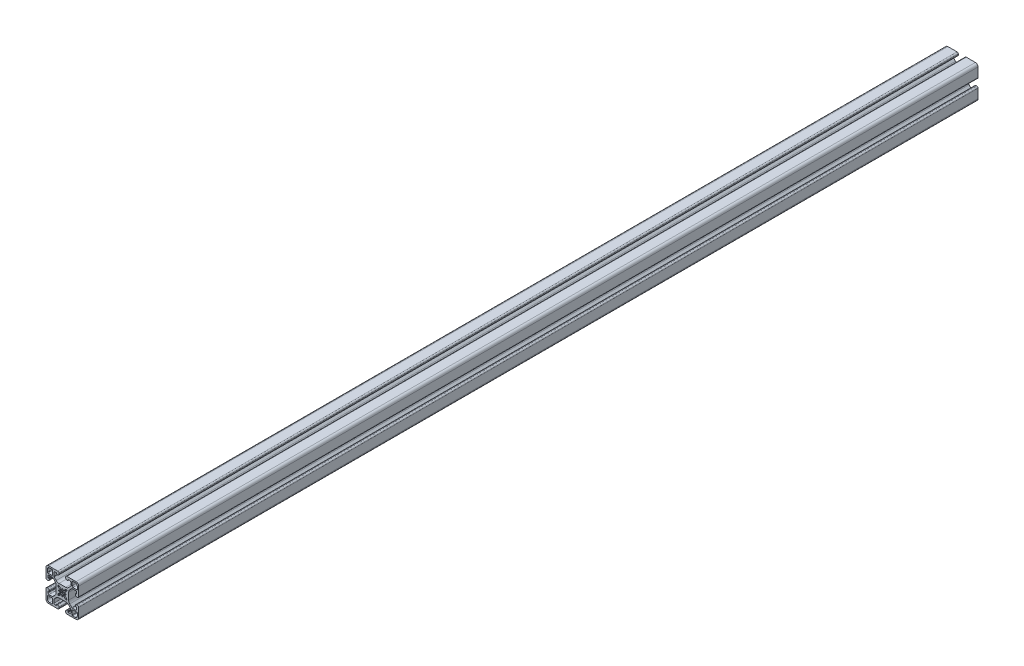
SolidWorks part; units mm, degrees
material "6005A-T61 Aluminum"
ref_plane "Front Plane" through (0, 0, 0) normal (0, 0, 1) x (1, 0, 0)
ref_plane "Top Plane" through (0, 0, 0) normal (0, 1, 0) x (1, 0, 0)
ref_plane "Right Plane" through (0, 0, 0) normal (1, 0, 0) x (0, 0, -1)
sketch "Sketch1" plane through (0, 0, 0) normal (0, 0, 1) x (1, 0, 0)
  line L0 (-5.1263, -3.712) -> (-5.4393, -4.8481)
  line L1 (-3.0049, -1.5907) -> (-5.1263, -3.712)
  line L2 (-4.0876, -0.4923) -> (-3.3421, -0.625)
  line L3 (-3.3421, 0.625) -> (-4.0876, 0.4923)
  line L4 (-5.1263, 3.712) -> (-3.0049, 1.5907)
  line L5 (-5.4393, 4.8481) -> (-5.1263, 3.712)
  line L6 (-3.712, 5.1263) -> (-4.8481, 5.4393)
  line L7 (-1.5907, 3.0049) -> (-3.712, 5.1263)
  line L8 (-0.4923, 4.0876) -> (-0.625, 3.3421)
  line L9 (0.625, 3.3421) -> (0.4923, 4.0876)
  line L10 (3.712, 5.1263) -> (1.5907, 3.0049)
  line L11 (4.8481, 5.4393) -> (3.712, 5.1263)
  line L12 (5.1263, 3.712) -> (5.4393, 4.8481)
  line L13 (3.0049, 1.5907) -> (5.1263, 3.712)
  line L14 (4.0876, 0.4923) -> (3.3421, 0.625)
  line L15 (3.3421, -0.625) -> (4.0876, -0.4923)
  line L16 (5.1263, -3.712) -> (3.0049, -1.5907)
  line L17 (5.4393, -4.8481) -> (5.1263, -3.712)
  line L18 (3.712, -5.1263) -> (4.8481, -5.4393)
  line L19 (1.5907, -3.0049) -> (3.712, -5.1263)
  line L20 (0.4923, -4.0876) -> (0.625, -3.3421)
  line L21 (-0.625, -3.3421) -> (-0.4923, -4.0876)
  line L22 (-3.712, -5.1263) -> (-1.5907, -3.0049)
  line L23 (-4.8481, -5.4393) -> (-3.712, -5.1263)
  line L24 (-12.4898, 18.345) -> (-15.545, 18.345)
  line L25 (-11.8598, 13.1298) -> (-11.8598, 17.715)
  line L26 (-17.715, 11.8598) -> (-13.1298, 11.8598)
  line L27 (-18.345, 15.545) -> (-18.345, 12.4898)
  line L28 (18.345, 12.4898) -> (18.345, 15.545)
  line L29 (13.1298, 11.8598) -> (17.715, 11.8598)
  line L30 (11.8598, 17.715) -> (11.8598, 13.1298)
  line L31 (15.545, 18.345) -> (12.4898, 18.345)
  line L32 (-18.345, -12.4898) -> (-18.345, -15.545)
  line L33 (-13.1298, -11.8598) -> (-17.715, -11.8598)
  line L34 (-11.8598, -17.715) -> (-11.8598, -13.1298)
  line L35 (-15.545, -18.345) -> (-12.4898, -18.345)
  line L36 (12.4898, -18.345) -> (15.545, -18.345)
  line L37 (11.8598, -13.1298) -> (11.8598, -17.715)
  line L38 (17.715, -11.8598) -> (13.1298, -11.8598)
  line L39 (18.345, -15.545) -> (18.345, -12.4898)
  line L40 (-5.63, 20) -> (-16.83, 20)
  line L41 (-20, 16.83) -> (-20, 5.63)
  line L42 (-18.43, 4.06) -> (-17.57, 4.06)
  line L43 (-16, 5.63) -> (-16, 6.605)
  line L44 (-16.25, 6.855) -> (-17.25, 6.855)
  line L45 (-17.5, 7.105) -> (-17.5, 9.015)
  line L46 (-16.23, 10.285) -> (-12.2162, 10.285)
  line L47 (-11.5869, 10.0243) -> (-9.0762, 7.5137)
  line L48 (-7.685, 4.1549) -> (-7.685, -4.1549)
  line L49 (-9.0762, -7.5137) -> (-11.5869, -10.0243)
  line L50 (-12.2162, -10.285) -> (-16.23, -10.285)
  line L51 (-17.5, -9.015) -> (-17.5, -7.105)
  line L52 (-17.25, -6.855) -> (-16.25, -6.855)
  line L53 (-16, -6.605) -> (-16, -5.63)
  line L54 (-17.57, -4.06) -> (-18.43, -4.06)
  line L55 (-20, -5.63) -> (-20, -16.83)
  line L56 (-16.83, -20) -> (-5.63, -20)
  line L57 (-4.06, -18.43) -> (-4.06, -17.57)
  line L58 (-5.63, -16) -> (-6.605, -16)
  line L59 (-6.855, -16.25) -> (-6.855, -17.25)
  line L60 (-7.105, -17.5) -> (-9.015, -17.5)
  line L61 (-10.285, -16.23) -> (-10.285, -12.2162)
  line L62 (-10.0243, -11.5869) -> (-7.5137, -9.0762)
  line L63 (-4.1549, -7.685) -> (4.1549, -7.685)
  line L64 (7.5137, -9.0762) -> (10.0243, -11.5869)
  line L65 (10.285, -12.2162) -> (10.285, -16.23)
  line L66 (9.015, -17.5) -> (7.105, -17.5)
  line L67 (6.855, -17.25) -> (6.855, -16.25)
  line L68 (6.605, -16) -> (5.63, -16)
  line L69 (4.06, -17.57) -> (4.06, -18.43)
  line L70 (5.63, -20) -> (16.83, -20)
  line L71 (20, -16.83) -> (20, -5.63)
  line L72 (18.43, -4.06) -> (17.57, -4.06)
  line L73 (16, -5.63) -> (16, -6.605)
  line L74 (16.25, -6.855) -> (17.25, -6.855)
  line L75 (17.5, -7.105) -> (17.5, -9.015)
  line L76 (16.23, -10.285) -> (12.2162, -10.285)
  line L77 (11.5869, -10.0243) -> (9.0762, -7.5137)
  line L78 (7.685, -4.1549) -> (7.685, 4.1549)
  line L79 (9.0762, 7.5137) -> (11.5869, 10.0243)
  line L80 (12.2162, 10.285) -> (16.23, 10.285)
  line L81 (17.5, 9.015) -> (17.5, 7.105)
  line L82 (17.25, 6.855) -> (16.25, 6.855)
  line L83 (16, 6.605) -> (16, 5.63)
  line L84 (17.57, 4.06) -> (18.43, 4.06)
  line L85 (20, 5.63) -> (20, 16.83)
  line L86 (16.83, 20) -> (5.63, 20)
  line L87 (4.06, 18.43) -> (4.06, 17.57)
  line L88 (5.63, 16) -> (6.605, 16)
  line L89 (6.855, 16.25) -> (6.855, 17.25)
  line L90 (7.105, 17.5) -> (9.015, 17.5)
  line L91 (10.285, 16.23) -> (10.285, 12.2162)
  line L92 (10.0243, 11.5869) -> (7.5137, 9.0762)
  line L93 (4.1549, 7.685) -> (-4.1549, 7.685)
  line L94 (-7.5137, 9.0762) -> (-10.0243, 11.5869)
  line L95 (-10.285, 12.2162) -> (-10.285, 16.23)
  line L96 (-9.015, 17.5) -> (-7.105, 17.5)
  line L97 (-6.855, 17.25) -> (-6.855, 16.25)
  line L98 (-6.605, 16) -> (-5.63, 16)
  line L99 (-4.06, 17.57) -> (-4.06, 18.43)
  arc A0 (-5.4393, -4.8481) -> (-4.8481, -5.4393) centre (-4.9497, -4.9497) ccw
  arc A1 (-3.3421, -0.625) -> (-3.0049, -1.5907) centre (0, 0) ccw
  arc A2 (-4.0876, 0.4923) -> (-4.0876, -0.4923) centre (-4, 0) ccw
  arc A3 (-3.0049, 1.5907) -> (-3.3421, 0.625) centre (0, 0) ccw
  arc A4 (-4.8481, 5.4393) -> (-5.4393, 4.8481) centre (-4.9497, 4.9497) ccw
  arc A5 (-0.625, 3.3421) -> (-1.5907, 3.0049) centre (0, 0) ccw
  arc A6 (0.4923, 4.0876) -> (-0.4923, 4.0876) centre (0, 4) ccw
  arc A7 (1.5907, 3.0049) -> (0.625, 3.3421) centre (0, 0) ccw
  arc A8 (5.4393, 4.8481) -> (4.8481, 5.4393) centre (4.9497, 4.9497) ccw
  arc A9 (3.3421, 0.625) -> (3.0049, 1.5907) centre (0, 0) ccw
  arc A10 (4.0876, -0.4923) -> (4.0876, 0.4923) centre (4, 0) ccw
  arc A11 (3.0049, -1.5907) -> (3.3421, -0.625) centre (0, 0) ccw
  arc A12 (4.8481, -5.4393) -> (5.4393, -4.8481) centre (4.9497, -4.9497) ccw
  arc A13 (0.625, -3.3421) -> (1.5907, -3.0049) centre (0, 0) ccw
  arc A14 (-0.4923, -4.0876) -> (0.4923, -4.0876) centre (0, -4) ccw
  arc A15 (-1.5907, -3.0049) -> (-0.625, -3.3421) centre (0, 0) ccw
  arc A16 (-15.545, 18.345) -> (-18.345, 15.545) centre (-15.545, 15.545) ccw
  arc A17 (-11.8598, 17.715) -> (-12.4898, 18.345) centre (-12.4898, 17.715) ccw
  arc A18 (-13.1298, 11.8598) -> (-11.8598, 13.1298) centre (-13.1298, 13.1298) ccw
  arc A19 (-18.345, 12.4898) -> (-17.715, 11.8598) centre (-17.715, 12.4898) ccw
  arc A20 (18.345, 15.545) -> (15.545, 18.345) centre (15.545, 15.545) ccw
  arc A21 (17.715, 11.8598) -> (18.345, 12.4898) centre (17.715, 12.4898) ccw
  arc A22 (11.8598, 13.1298) -> (13.1298, 11.8598) centre (13.1298, 13.1298) ccw
  arc A23 (12.4898, 18.345) -> (11.8598, 17.715) centre (12.4898, 17.715) ccw
  arc A24 (-18.345, -15.545) -> (-15.545, -18.345) centre (-15.545, -15.545) ccw
  arc A25 (-17.715, -11.8598) -> (-18.345, -12.4898) centre (-17.715, -12.4898) ccw
  arc A26 (-11.8598, -13.1298) -> (-13.1298, -11.8598) centre (-13.1298, -13.1298) ccw
  arc A27 (-12.4898, -18.345) -> (-11.8598, -17.715) centre (-12.4898, -17.715) ccw
  arc A28 (15.545, -18.345) -> (18.345, -15.545) centre (15.545, -15.545) ccw
  arc A29 (11.8598, -17.715) -> (12.4898, -18.345) centre (12.4898, -17.715) ccw
  arc A30 (13.1298, -11.8598) -> (11.8598, -13.1298) centre (13.1298, -13.1298) ccw
  arc A31 (18.345, -12.4898) -> (17.715, -11.8598) centre (17.715, -12.4898) ccw
  arc A32 (-4.06, 18.43) -> (-5.63, 20) centre (-5.63, 18.43) ccw
  arc A33 (-16.83, 20) -> (-20, 16.83) centre (-16.83, 16.83) ccw
  arc A34 (-20, 5.63) -> (-18.43, 4.06) centre (-18.43, 5.63) ccw
  arc A35 (-17.57, 4.06) -> (-16, 5.63) centre (-17.57, 5.63) ccw
  arc A36 (-16, 6.605) -> (-16.25, 6.855) centre (-16.25, 6.605) ccw
  arc A37 (-17.5, 7.105) -> (-17.25, 6.855) centre (-17.25, 7.105) ccw
  arc A38 (-16.23, 10.285) -> (-17.5, 9.015) centre (-16.23, 9.015) ccw
  arc A39 (-11.5869, 10.0243) -> (-12.2162, 10.285) centre (-12.2162, 9.395) ccw
  arc A40 (-7.685, 4.1549) -> (-9.0762, 7.5137) centre (-12.435, 4.1549) ccw
  arc A41 (-9.0762, -7.5137) -> (-7.685, -4.1549) centre (-12.435, -4.1549) ccw
  arc A42 (-12.2162, -10.285) -> (-11.5869, -10.0243) centre (-12.2162, -9.395) ccw
  arc A43 (-17.5, -9.015) -> (-16.23, -10.285) centre (-16.23, -9.015) ccw
  arc A44 (-17.25, -6.855) -> (-17.5, -7.105) centre (-17.25, -7.105) ccw
  arc A45 (-16.25, -6.855) -> (-16, -6.605) centre (-16.25, -6.605) ccw
  arc A46 (-16, -5.63) -> (-17.57, -4.06) centre (-17.57, -5.63) ccw
  arc A47 (-18.43, -4.06) -> (-20, -5.63) centre (-18.43, -5.63) ccw
  arc A48 (-20, -16.83) -> (-16.83, -20) centre (-16.83, -16.83) ccw
  arc A49 (-5.63, -20) -> (-4.06, -18.43) centre (-5.63, -18.43) ccw
  arc A50 (-4.06, -17.57) -> (-5.63, -16) centre (-5.63, -17.57) ccw
  arc A51 (-6.605, -16) -> (-6.855, -16.25) centre (-6.605, -16.25) ccw
  arc A52 (-7.105, -17.5) -> (-6.855, -17.25) centre (-7.105, -17.25) ccw
  arc A53 (-10.285, -16.23) -> (-9.015, -17.5) centre (-9.015, -16.23) ccw
  arc A54 (-10.0243, -11.5869) -> (-10.285, -12.2162) centre (-9.395, -12.2162) ccw
  arc A55 (-4.1549, -7.685) -> (-7.5137, -9.0762) centre (-4.1549, -12.435) ccw
  arc A56 (7.5137, -9.0762) -> (4.1549, -7.685) centre (4.1549, -12.435) ccw
  arc A57 (10.285, -12.2162) -> (10.0243, -11.5869) centre (9.395, -12.2162) ccw
  arc A58 (9.015, -17.5) -> (10.285, -16.23) centre (9.015, -16.23) ccw
  arc A59 (6.855, -17.25) -> (7.105, -17.5) centre (7.105, -17.25) ccw
  arc A60 (6.855, -16.25) -> (6.605, -16) centre (6.605, -16.25) ccw
  arc A61 (5.63, -16) -> (4.06, -17.57) centre (5.63, -17.57) ccw
  arc A62 (4.06, -18.43) -> (5.63, -20) centre (5.63, -18.43) ccw
  arc A63 (16.83, -20) -> (20, -16.83) centre (16.83, -16.83) ccw
  arc A64 (20, -5.63) -> (18.43, -4.06) centre (18.43, -5.63) ccw
  arc A65 (17.57, -4.06) -> (16, -5.63) centre (17.57, -5.63) ccw
  arc A66 (16, -6.605) -> (16.25, -6.855) centre (16.25, -6.605) ccw
  arc A67 (17.5, -7.105) -> (17.25, -6.855) centre (17.25, -7.105) ccw
  arc A68 (16.23, -10.285) -> (17.5, -9.015) centre (16.23, -9.015) ccw
  arc A69 (11.5869, -10.0243) -> (12.2162, -10.285) centre (12.2162, -9.395) ccw
  arc A70 (7.685, -4.1549) -> (9.0762, -7.5137) centre (12.435, -4.1549) ccw
  arc A71 (9.0762, 7.5137) -> (7.685, 4.1549) centre (12.435, 4.1549) ccw
  arc A72 (12.2162, 10.285) -> (11.5869, 10.0243) centre (12.2162, 9.395) ccw
  arc A73 (17.5, 9.015) -> (16.23, 10.285) centre (16.23, 9.015) ccw
  arc A74 (17.25, 6.855) -> (17.5, 7.105) centre (17.25, 7.105) ccw
  arc A75 (16.25, 6.855) -> (16, 6.605) centre (16.25, 6.605) ccw
  arc A76 (16, 5.63) -> (17.57, 4.06) centre (17.57, 5.63) ccw
  arc A77 (18.43, 4.06) -> (20, 5.63) centre (18.43, 5.63) ccw
  arc A78 (20, 16.83) -> (16.83, 20) centre (16.83, 16.83) ccw
  arc A79 (5.63, 20) -> (4.06, 18.43) centre (5.63, 18.43) ccw
  arc A80 (4.06, 17.57) -> (5.63, 16) centre (5.63, 17.57) ccw
  arc A81 (6.605, 16) -> (6.855, 16.25) centre (6.605, 16.25) ccw
  arc A82 (7.105, 17.5) -> (6.855, 17.25) centre (7.105, 17.25) ccw
  arc A83 (10.285, 16.23) -> (9.015, 17.5) centre (9.015, 16.23) ccw
  arc A84 (10.0243, 11.5869) -> (10.285, 12.2162) centre (9.395, 12.2162) ccw
  arc A85 (4.1549, 7.685) -> (7.5137, 9.0762) centre (4.1549, 12.435) ccw
  arc A86 (-7.5137, 9.0762) -> (-4.1549, 7.685) centre (-4.1549, 12.435) ccw
  arc A87 (-10.285, 12.2162) -> (-10.0243, 11.5869) centre (-9.395, 12.2162) ccw
  arc A88 (-9.015, 17.5) -> (-10.285, 16.23) centre (-9.015, 16.23) ccw
  arc A89 (-6.855, 17.25) -> (-7.105, 17.5) centre (-7.105, 17.25) ccw
  arc A90 (-6.855, 16.25) -> (-6.605, 16) centre (-6.605, 16.25) ccw
  arc A91 (-5.63, 16) -> (-4.06, 17.57) centre (-5.63, 17.57) ccw
extrude "Extrude1" add sketch "Sketch1" along normal mid plane 1100
ref_axis "Hole RS" through (0, 0, 550) along (0, 0, -1)
ref_plane "Plane S" through (0, 0, 0) normal (0, 1, 0) x (1, 0, 0)
ref_plane "Plane R" through (0, 0, 0) normal (-1, 0, 0) x (0, 0, 1)
ref_plane "Left End Plane" through (0, 0, 550) normal (0, 0, 1) x (1, 0, 0)
ref_plane "Right End Plane" through (0, 0, -550) normal (0, 0, -1) x (-1, 0, 0)
